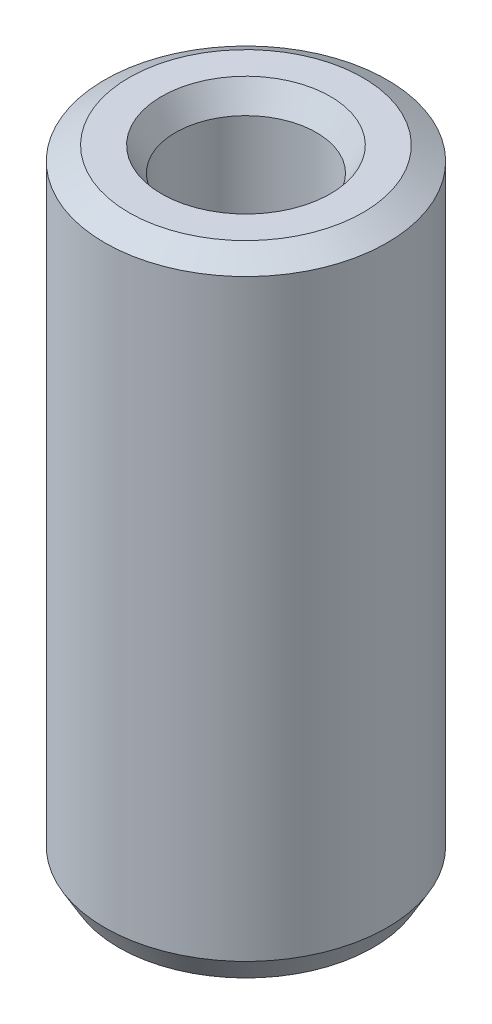
SolidWorks part; units mm, degrees
ref_plane "Front Plane" through (0, 0, 0) normal (0, 0, 1) x (1, 0, 0)
ref_plane "Top Plane" through (0, 0, 0) normal (0, 1, 0) x (1, 0, 0)
ref_plane "Right Plane" through (0, 0, 0) normal (1, 0, 0) x (0, 0, -1)
sketch "Sketch1" plane through (0, 0, 0) normal (0, 1, 0) x (1, 0, 0)
  circle A0 centre (0, 0) radius 12.5
  dimension "SLEEVE_OD" = 25
extrude "Boss-Extrude1" add sketch "Sketch1" along normal blind 55.8873
sketch "Sketch2" plane through (0, 0, 0) normal (0, 1, 0) x (1, 0, 0)
  circle A0 centre (0, 0) radius 6.2344
  dimension "BORE_D" = 12.4688
extrude "Cut-Extrude1" cut sketch "Sketch2" along normal through all
chamfer "Chamfer1" distance 1.2391 angle 60 4 edges at (0, 55.8873, 6.2344) (0, 0, 6.2344) (0, 0, 12.5) (0, 55.8873, 12.5) first distance on face at (0, 55.8873, 6.2344) first distance on face at (0, 0, 6.2344) first distance on face at (0, 55.8873, 12.5)
